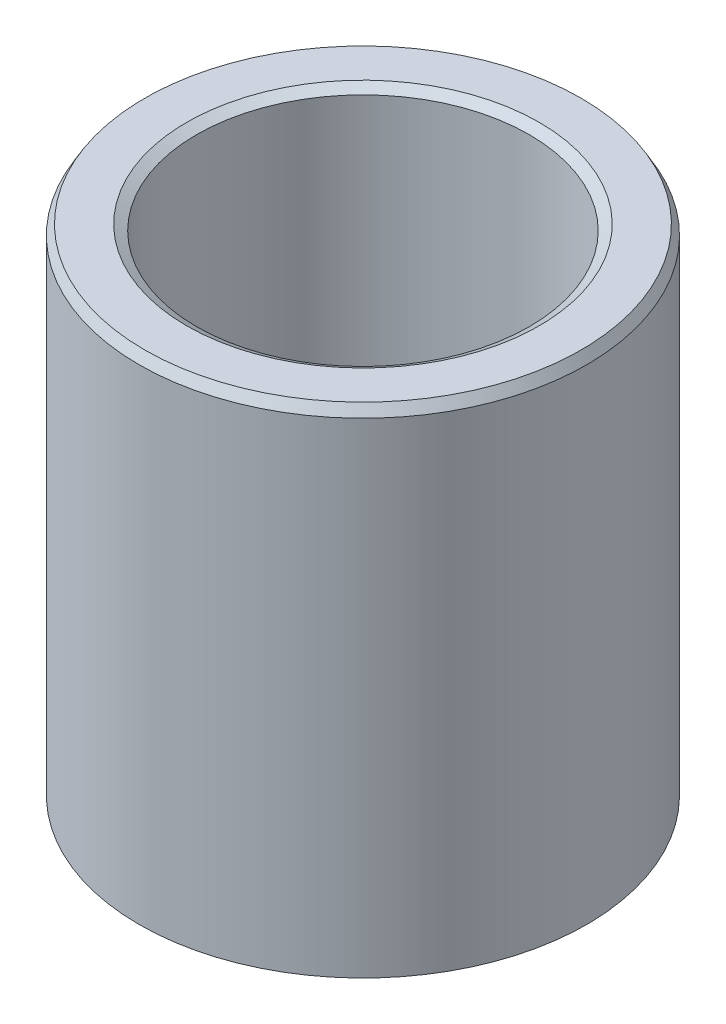
SolidWorks part; units mm, degrees
ref_plane "Front Plane" through (0, 0, 0) normal (0, 0, 1) x (1, 0, 0)
ref_plane "Top Plane" through (0, 0, 0) normal (0, 1, 0) x (1, 0, 0)
ref_plane "Right Plane" through (0, 0, 0) normal (1, 0, 0) x (0, 0, -1)
sketch "Sketch1" plane through (0, 0, 0) normal (0, 1, 0) x (1, 0, 0)
  circle A0 centre (0, 0) radius 22.5
  dimension "SLEEVE_OD" = 45
extrude "Boss-Extrude1" add sketch "Sketch1" along normal blind 50.2972
sketch "Sketch2" plane through (0, 0, 0) normal (0, 1, 0) x (1, 0, 0)
  circle A0 centre (0, 0) radius 16.7217
  dimension "BORE_D" = 33.4433
extrude "Cut-Extrude1" cut sketch "Sketch2" along normal through all
chamfer "Chamfer1" distance 0.9951 angle 30 4 edges at (0, 50.2972, 16.7217) (0, 0, 16.7217) (0, 0, 22.5) (0, 50.2972, 22.5) first distance on face at (0, 50.2972, 16.7217) first distance on face at (0, 0, 16.7217) first distance on face at (0, 50.2972, 22.5)
